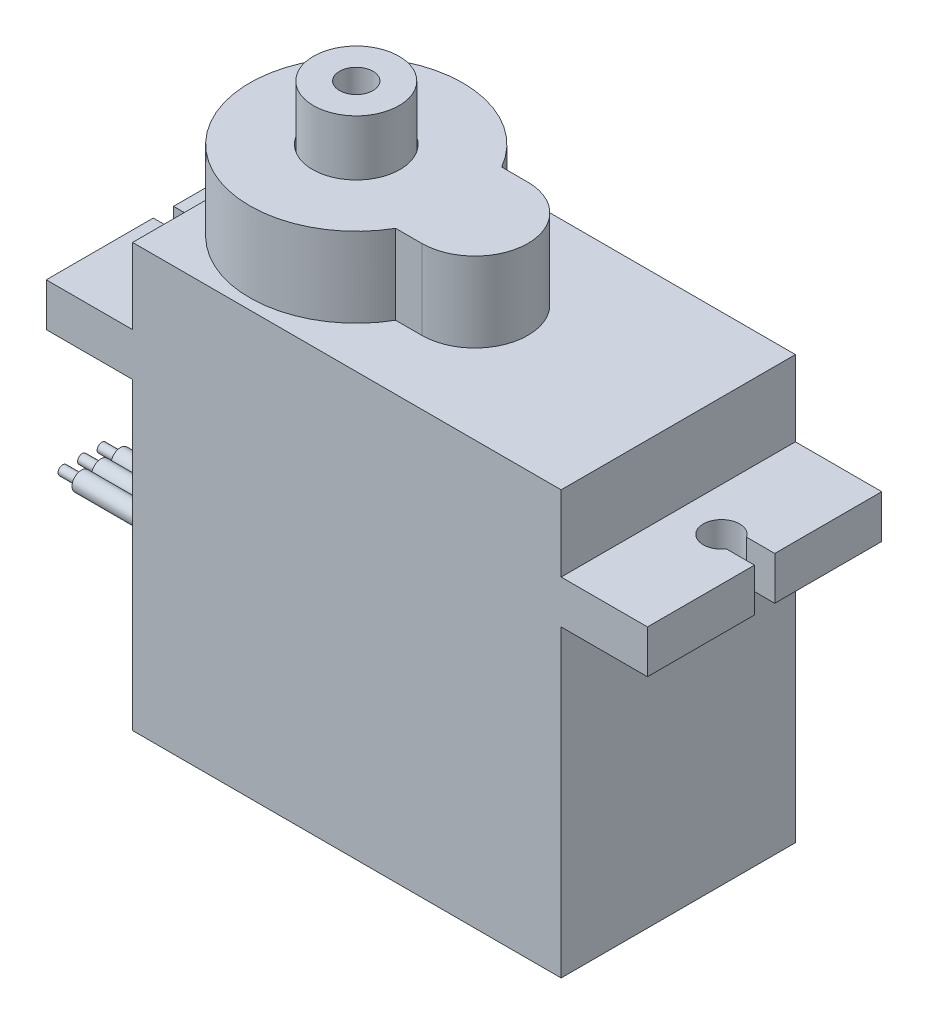
SolidWorks part; units mm, degrees
ref_plane "Front Plane" through (0, 0, 0) normal (0, 0, 1) x (1, 0, 0)
ref_plane "Top Plane" through (0, 0, 0) normal (0, 1, 0) x (1, 0, 0)
ref_plane "Right Plane" through (0, 0, 0) normal (1, 0, 0) x (0, 0, -1)
ref_axis "X-Axis" through (-88.99, 0, 0) along (1, 0, 0)
ref_axis "Y-Axis" through (0, 0, -88.99) along (0, 0, 1)
ref_axis "Z-Axis" through (0, 55, 0) along (0, -1, 0)
sketch "Sketch1" plane through (0, 0, 0) normal (0, 0, 1) x (1, 0, 0)
  line L0 (0, 0) -> (0, 12.96) construction
  line L1 (-7.13, 6.38) -> (15.9, 6.38)
  line L2 (-7.13, 6.38) -> (-7.13, 2.32)
  line L3 (-7.13, -16.34) -> (15.9, -16.34)
  line L4 (15.9, 6.38) -> (15.9, 2.32)
  line L5 (15.9, 2.32) -> (20.54, 2.32)
  line L6 (-11.77, 2.32) -> (-7.13, 2.32)
  line L7 (-11.77, 2.32) -> (-11.77, 0)
  line L8 (-11.77, 0) -> (-7.13, 0)
  line L9 (20.54, 2.32) -> (20.54, 0)
  line L10 (15.9, 0) -> (20.54, 0)
  line L11 (-7.13, 0) -> (-7.13, -16.34)
  line L12 (15.9, 0) -> (15.9, -16.34)
  line L14 (15.9, 0) -> (-7.13, 0) construction
  point P3 (4.385, 0)
  dimension "D1" = 2.32
  dimension "D2" = 32.31
  dimension "D3" = 23.03
  dimension "D4" = 16.34
  dimension "D5" = 22.72
  dimension "D6" = 7.13
  dimension "D7" = 15.9
  dimension "D10" = 29.3
  dimension "D11" = 4.385
extrude "Boss-Extrude1" add sketch "Sketch1" along normal mid plane 12.59
sketch "Sketch2" plane through (0, 6.38, 0) normal (0, 1, 0) x (1, 0, 0)
  line L0 (-1.405, 0) -> (4.97, 0) construction
  line L1 (3.5602, -2.85) -> (4.97, -2.85)
  line L2 (4.97, 2.85) -> (3.5602, 2.85)
  line L3 (-1.405, 0) -> (-7.13, 0) construction
  line L4 (4.97, 0) -> (7.82, 0) construction
  line L5 (-7.13, -6.295) -> (-7.13, 6.295) construction
  arc A0 (3.5602, 2.85) -> (3.5602, -2.85) centre (-1.405, 0) ccw
  arc A1 (4.97, -2.85) -> (4.97, 2.85) centre (4.97, 0) ccw
  dimension "D1" = 11.45
  dimension "D2" = 5.7
  dimension "D3" = 14.95
extrude "Boss-Extrude2" add sketch "Sketch2" along normal blind 4.28
sketch "Sketch4" plane through (0, 0, 0) normal (0, 1, 0) x (1, 0, 0)
  line L0 (-7.13, 0) -> (-9.45, 0) construction
  line L1 (-11.77, -6.295) -> (-11.77, 6.295) construction
  line L2 (-10.2585, 0.545) -> (-11.77, 0.545)
  line L3 (-10.2585, 0.545) -> (-10.2585, -0.545)
  line L4 (-10.2585, -0.545) -> (-11.77, -0.545)
  line L5 (-11.77, 0.545) -> (-11.77, -0.545)
  line L8 (-9.45, 0) -> (-10.2585, 0) construction
  line L9 (-9.45, 0) -> (-11.77, 0) construction
  arc A0 (3.5602, 2.85) -> (3.5602, -2.85) centre (-1.405, 0) ccw construction
  circle A1 centre (-9.45, 0) radius 0.975
  dimension "D1" = 1.09
  dimension "D2" = 1.95
extrude "Cut-Extrude1" cut sketch "Sketch4" along normal through all contours A1 | L4 L5 L2 L3
sketch "Sketch5" plane through (0, -16.34, 0) normal (0, -1, 0) x (1, 0, 0)
  line L0 (15.9, 6.295) -> (-7.13, -6.295) construction
  line L17 (-5.49, 4.35) -> (14.26, 4.35) construction
  line L18 (-5.49, 4.35) -> (-5.49, -4.35) construction
  line L19 (-5.49, -4.35) -> (14.26, -4.35) construction
  line L20 (14.26, 4.35) -> (14.26, -4.35) construction
  line L21 (-5.49, 4.35) -> (14.26, -4.35) construction
  circle A0 centre (-5.49, 4.35) radius 1
  circle A1 centre (-5.49, -4.35) radius 1
  circle A2 centre (14.26, -4.35) radius 1
  circle A3 centre (14.26, 4.35) radius 1
  circle A4 centre (-5.49, 4.35) radius 0.975
  circle A5 centre (-5.49, -4.35) radius 0.975
  circle A6 centre (14.26, -4.35) radius 0.975
  circle A7 centre (14.26, 4.35) radius 0.975
  point P36 (4.385, 0)
  dimension "D1" = 0.025
  dimension "D4" = 1.95
  dimension "D5" = 19.75
  dimension "D6" = 8.7
extrude "Cut-Extrude2" cut sketch "Sketch5" against normal blind 1
sketch "Sketch6" plane through (-7.13, 0, 0) normal (-1, 0, 0) x (0, 0, 1)
  line L0 (-1.05, -11.34) -> (1.05, -11.34) construction
  line L1 (0, -11.84) -> (0, -16.34) construction
  line L3 (6.295, -16.34) -> (-6.295, -16.34) construction
  circle A0 centre (0, -11.34) radius 0.5
  circle A1 centre (1.05, -11.34) radius 0.5
  circle A2 centre (-1.05, -11.34) radius 0.5
  dimension "D3" = 1
  dimension "D1" = 4.5
  dimension "D2" = 2.1
extrude "Boss-Extrude4" add sketch "Sketch6" along normal blind 8
sketch "Sketch7" plane through (-15.13, 0, 0) normal (-1, 0, 0) x (0, 0, 1)
  circle A0 centre (0, -11.34) radius 0.25
  circle A1 centre (1.05, -11.34) radius 0.25
  circle A2 centre (-1.05, -11.34) radius 0.25
  dimension "D1" = 0.5
extrude "Boss-Extrude5" add sketch "Sketch7" along normal blind 1
sketch "Sketch3" plane through (0, 10.66, 0) normal (0, 1, 0) x (1, 0, 0)
  line L0 (4.7718, -0.52) -> (4.97, -0.52)
  line L1 (4.97, 0.52) -> (4.7718, 0.52)
  line L2 (5.49, 0) -> (7.82, 0) construction
  line L3 (-4.8, 0) -> (-7.13, 0) construction
  arc A0 (4.7718, 0.52) -> (4.7718, -0.52) centre (0, 0) ccw
  arc A1 (4.97, -0.52) -> (4.97, 0.52) centre (4.97, 0) ccw
  arc A2 (4.97, -2.85) -> (4.97, 2.85) centre (4.97, 0) ccw construction
  arc A3 (3.5602, 2.85) -> (3.5602, -2.85) centre (-1.405, 0) ccw construction
  dimension "D1" = 9.6
fillet "Fillet1" radius 0.3 4 edges at (14.26, -16.34, -5.325) (14.26, -16.34, 3.375) (-5.49, -16.34, -5.325) (-5.49, -16.34, 3.375)
sketch "Sketch12" plane through (0, 10.66, 0) normal (0, 1, 0) x (1, 0, 0)
  circle A0 centre (-1.405, 0) radius 2.3
  circle A1 centre (-1.405, 0) radius 0.9
  dimension "D1" = 4.6
  dimension "D2" = 1.8
extrude "Boss-Extrude6" add sketch "Sketch12" along normal blind 2.95 and the other way blind 1 separate body
sketch "Sketch13" plane through (0, 13.61, 0) normal (0, 1, 0) x (1, 0, 0)
  circle A0 centre (-1.405, 0) radius 2.35
  dimension "D1" = 4.7
extrude "Cut-Extrude5" cut sketch "Sketch13" against normal blind 5
ref_plane "Plan1" through (4.385, 0, 0) normal (-1, 0, 0) x (0, 0, 1)
mirror "Symétrie1" about plane through (4.385, 0, 0) normal (-1, 0, 0) of "Cut-Extrude1"
